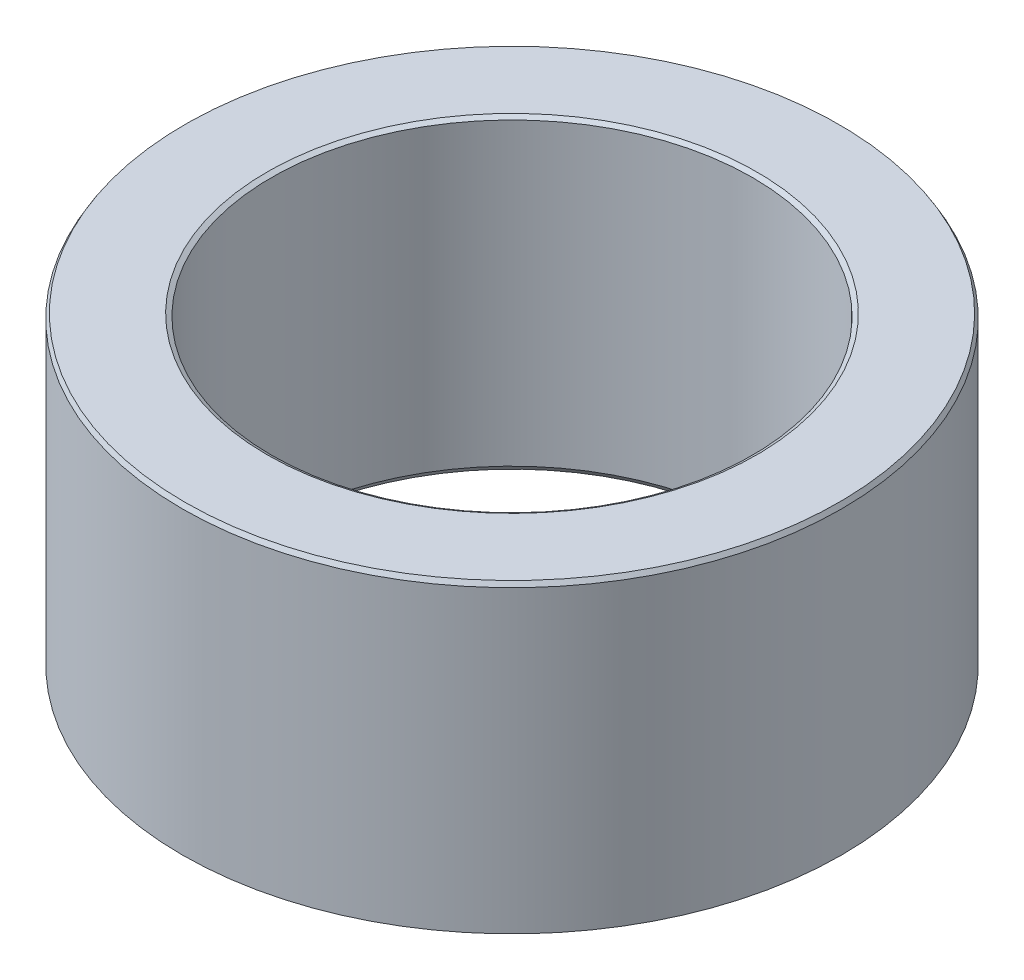
SolidWorks part; units mm, degrees
ref_plane "Front Plane" through (0, 0, 0) normal (0, 0, 1) x (1, 0, 0)
ref_plane "Top Plane" through (0, 0, 0) normal (0, 1, 0) x (1, 0, 0)
ref_plane "Right Plane" through (0, 0, 0) normal (1, 0, 0) x (0, 0, -1)
sketch "Sketch1" plane through (0, 0, 0) normal (0, 1, 0) x (1, 0, 0)
  circle A0 centre (0, 0) radius 42.5
  dimension "SLEEVE_OD" = 85
extrude "Boss-Extrude1" add sketch "Sketch1" along normal blind 39.5457
sketch "Sketch2" plane through (0, 0, 0) normal (0, 1, 0) x (1, 0, 0)
  circle A0 centre (0, 0) radius 31.0035
  dimension "BORE_D" = 62.007
extrude "Cut-Extrude1" cut sketch "Sketch2" along normal through all
chamfer "Chamfer1" distance 0.5713 angle 30 4 edges at (0, 39.5457, 31.0035) (0, 0, 31.0035) (0, 0, 42.5) (0, 39.5457, 42.5) first distance on face at (0, 39.5457, 31.0035) first distance on face at (0, 0, 31.0035) first distance on face at (0, 39.5457, 42.5)
